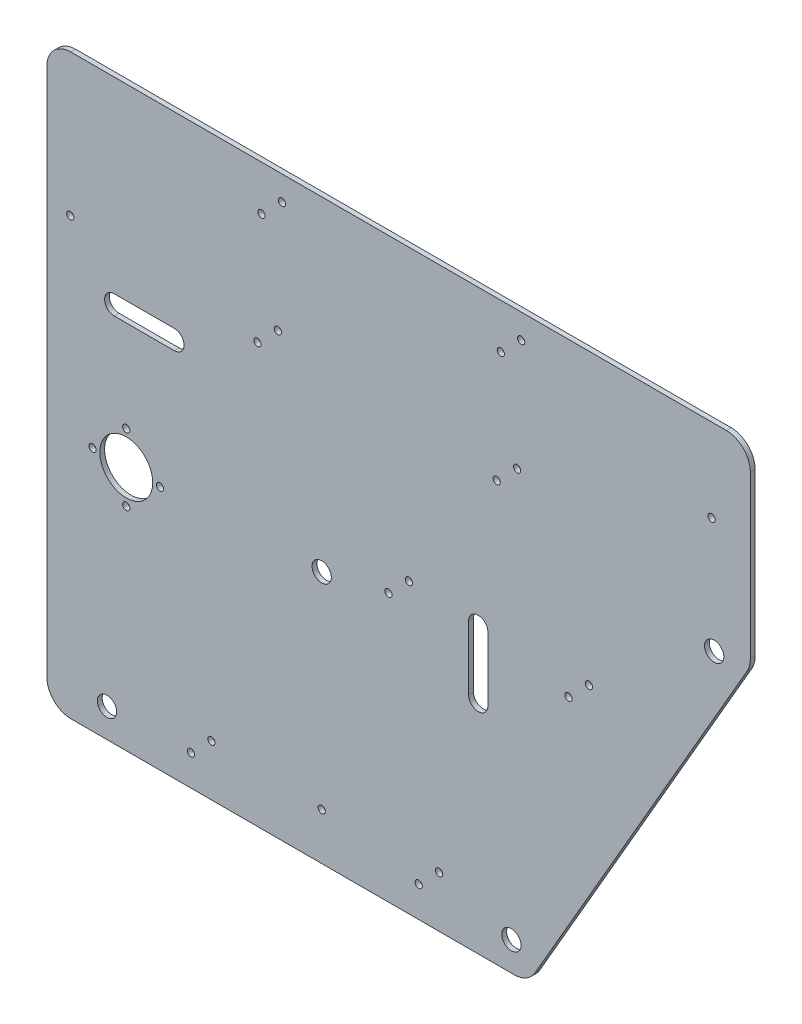
SolidWorks part; units mm, degrees
ref_plane "Front Plane" through (0, 0, 0) normal (0, 0, 1) x (1, 0, 0)
ref_plane "Top Plane" through (0, 0, 0) normal (0, 1, 0) x (1, 0, 0)
ref_plane "Right Plane" through (0, 0, 0) normal (1, 0, 0) x (0, 0, -1)
sketch "Sketch1" plane through (0, 0, 0) normal (0, 0, 1) x (1, 0, 0)
  line L0 (100, 80) -> (192.376, 80)
  line L1 (-100, -80) -> (100, -80)
  line L2 (-100, -80) -> (-100, 80)
  line L3 (-100, 80) -> (100, 80)
  line L4 (100, -80) -> (100, 80)
  line L5 (-100, -80) -> (100, 80) construction
  line L6 (-100, 80) -> (100, -80) construction
  line L7 (192.376, 80) -> (100, -80)
  line L8 (100, 80) -> (100, -80)
  line L10 (-100, 80) -> (192.376, 80)
  line L11 (-100, 80) -> (-100, 110)
  line L12 (-100, 110) -> (192.376, 110)
  line L13 (192.376, 80) -> (192.376, 110)
  point P0 (0, 0)
  dimension "D1" = 160
  dimension "D2" = 200
  dimension "D3" = 30
  dimension "D4" = 30
extrude "Boss-Extrude1" add sketch "Sketch1" along normal blind 2 contours L1 L4 L3 L2 | L7 L0 L4 | L11 L10 L13 L12 region at (0, 0, 0) region at (130.792, 26.6667, 0)
sketch "Sketch2" plane through (0, 0, 2) normal (0, 0, 1) x (1, 0, 0)
  line L0 (-100, -80) -> (100, -80) construction
  line L1 (192.376, 80) -> (100, -80) construction
  line L2 (79.2904, 11.2418) -> (79.2904, 37.9086) construction
  line L3 (-100, -80) -> (-100, 110) construction
  line L4 (-72, 78) -> (-47, 78) construction
  line L7 (-100, 110) -> (192.376, 110) construction
  line L8 (75.2904, 11.2418) -> (75.2904, 37.9086)
  line L9 (-72, 82) -> (-47, 82)
  line L10 (-72, 74) -> (-47, 74)
  line L11 (-100, -80) -> (-100, 110) construction
  line L12 (83.2904, 11.2418) -> (83.2904, 37.9086)
  circle A0 centre (93.0718, -68) radius 4
  circle A1 centre (177.3649, 78) radius 4
  circle A2 centre (-67, 22) radius 11
  circle A3 centre (-75, -68) radius 4
  circle A4 centre (-53, 22) radius 1.5
  circle A5 centre (-67, 36) radius 1.5
  circle A6 centre (-81, 22) radius 1.5
  circle A7 centre (-67, 8) radius 1.5
  circle A11 centre (54.5495, -67.2426) radius 1.5
  circle A12 centre (63.0348, -58.7574) radius 1.5
  circle A13 centre (14.2259, -60.5) radius 1.5
  circle A14 centre (-40.1271, -67.2426) radius 1.5
  circle A15 centre (-31.6419, -58.7574) radius 1.5
  circle A16 centre (-90.2956, 101.0243) radius 1.5
  circle A17 centre (-12.4828, 94.2817) radius 1.5
  circle A18 centre (-3.9975, 102.767) radius 1.5
  circle A19 centre (86.9654, 94.2817) radius 1.5
  circle A20 centre (95.4507, 102.767) radius 1.5
  circle A21 centre (41.9695, 31.2817) radius 1.5
  circle A22 centre (50.4548, 39.767) radius 1.5
  circle A23 centre (-39.813, 31.2817) radius 1.5 construction
  circle A24 centre (-31.3277, 39.767) radius 1.5 construction
  circle A25 centre (116.8113, 31.2817) radius 1.5
  circle A26 centre (125.2966, 39.767) radius 1.5
  circle A27 centre (79.2904, 25) radius 4 construction
  circle A28 centre (14.2259, 25) radius 4
  arc A29 (-72, 82) -> (-72, 74) centre (-72, 78) ccw
  arc A30 (-47, 74) -> (-47, 82) centre (-47, 78) ccw
  circle A31 centre (176.3056, 125.4889) radius 1.5
  arc A32 (75.2904, 11.2418) -> (83.2904, 11.2418) centre (79.2904, 11.2418) ccw
  arc A33 (83.2904, 37.9086) -> (75.2904, 37.9086) centre (79.2904, 37.9086) ccw
  circle A34 centre (-10.7791, 141.3442) radius 1.5
  circle A35 centre (-2.2938, 149.8294) radius 1.5
  circle A36 centre (88.6691, 141.3442) radius 1.5
  circle A37 centre (97.1544, 149.8294) radius 1.5
  point P26 (-59.5, 78)
  point P87 (79.2904, 24.5752)
  point P107 (0, 0)
  point P108 (176.3056, 125.4889)
  dimension "D3" = 8
  dimension "D4" = 8
  dimension "D9" = 22
  dimension "D10" = 8
  dimension "D12" = 3
  dimension "D13" = 3
  dimension "D14" = 3
  dimension "D15" = 3
  dimension "D16" = 14
  dimension "D20" = 8
  dimension "D22" = 4
  dimension "D25" = 3
  dimension "D26" = 3
  dimension "D29" = 8
  dimension "D28" = 3
  dimension "D1" = 12
  dimension "D2" = 12
  dimension "D5" = 32
  dimension "D6" = 12
  dimension "D7" = 88
  dimension "D8" = 33
  dimension "D11" = 12
  dimension "D17" = 14
  dimension "D18" = 14
  dimension "D19" = 14
  dimension "D21" = 85
  dimension "D23" = 28
  dimension "D24" = 25
  dimension "D27" = 25
  dimension "D30" = 8
extrude "Cut-Extrude1" cut sketch "Sketch2" against normal blind 3
sketch "Sketch4" plane through (0, 0, 2) normal (0, 0, 1) x (1, 0, 0)
  line L0 (192.376, 80) -> (192.376, 110) construction
  line L1 (-100, 110) -> (192.376, 110)
  line L2 (-100, 110) -> (-100, 160)
  line L3 (-100, 160) -> (192.376, 160)
  line L4 (192.376, 110) -> (192.376, 160)
  dimension "D1" = 50
extrude "Boss-Extrude2" add sketch "Sketch4" against normal blind 2
fillet "Fillet1" radius 10 5 edges at (192.376, 160, 1) (192.376, 80, 1) (100, -80, 1) (-100, -80, 1) (-100, 160, 1)
sketch "Sketch5" plane through (0, 0, 2) normal (0, 0, 1) x (1, 0, 0)
  circle A2 centre (-10.7791, 141.3442) radius 1.5
  circle A3 centre (-2.2938, 149.8294) radius 1.5
  circle A4 centre (88.6691, 141.3442) radius 1.5
  circle A5 centre (97.1544, 149.8294) radius 1.5
  circle A6 centre (176.3056, 125.4889) radius 1.5
  dimension "D1" = 3
extrude "Cut-Extrude2" cut sketch "Sketch5" against normal blind 11
